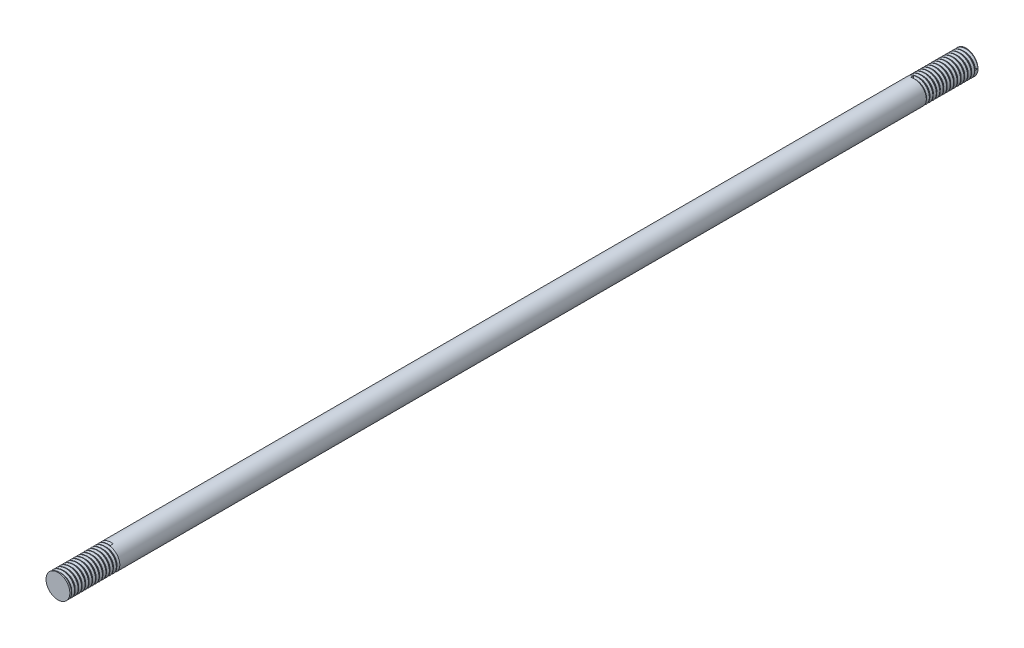
SolidWorks part; units mm, degrees
ref_plane "Front Plane" through (0, 0, 0) normal (0, 0, 1) x (1, 0, 0)
ref_plane "Top Plane" through (0, 0, 0) normal (0, 1, 0) x (1, 0, 0)
ref_plane "Right Plane" through (0, 0, 0) normal (1, 0, 0) x (0, 0, -1)
sketch "Sketch1" plane through (0, 0, 0) normal (0, 0, 1) x (1, 0, 0)
  circle A0 centre (0, 0) radius 6
  dimension "D1" = 12
extrude "Boss-Extrude1" add sketch "Sketch1" along normal blind 457.2
thread "Thread1" pitch 1.75 method cut profile "Thread Profile2" start angle 0, offset 0, length 25, pitch 1.75, diameter 12
ref_plane "Plane2" through (-6, 0, 457.2) normal (0, -1, 0) x (-1, 0, 0)
sketch "Thread Profile2" plane through (-6, 0, 457.2) normal (0, -1, 0) x (-1, 0, 0)
  line L0 (0, 0) -> (0, 1.75) construction
  line L11 (0, 0) -> (0, 1.5312)
  line L12 (0, 1.5312) -> (-0.9472, 0.9844)
  line L13 (-0.9472, 0.9844) -> (-0.9472, 0.5469)
  line L15 (-0.9472, 0.5469) -> (0, 0)
  line L17 (-0.9472, 0.7656) -> (0, 0.7656) construction
  point P2 (0, 0)
  dimension "Pitch" = 1.75
  dimension "Profile_Angle" = 60
  dimension "Profile_Land" = 0.4375
  dimension "Profile_Height" = 0.9472
thread "Thread2" pitch 1.75 method cut profile "Thread Profile3" start angle 0, offset 0, length 25, pitch 1.75, diameter 12
ref_plane "Plane3" through (6, 0, 0) normal (0, -1, 0) x (1, 0, 0)
sketch "Thread Profile3" plane through (6, 0, 0) normal (0, -1, 0) x (1, 0, 0)
  line L0 (0, 0) -> (0, 1.75) construction
  line L11 (0, 0) -> (0, 1.5312)
  line L12 (0, 1.5312) -> (-0.9472, 0.9844)
  line L13 (-0.9472, 0.9844) -> (-0.9472, 0.5469)
  line L15 (-0.9472, 0.5469) -> (0, 0)
  line L17 (-0.9472, 0.7656) -> (0, 0.7656) construction
  point P2 (0, 0)
  dimension "Pitch" = 1.75
  dimension "Profile_Angle" = 60
  dimension "Profile_Land" = 0.4375
  dimension "Profile_Height" = 0.9472
